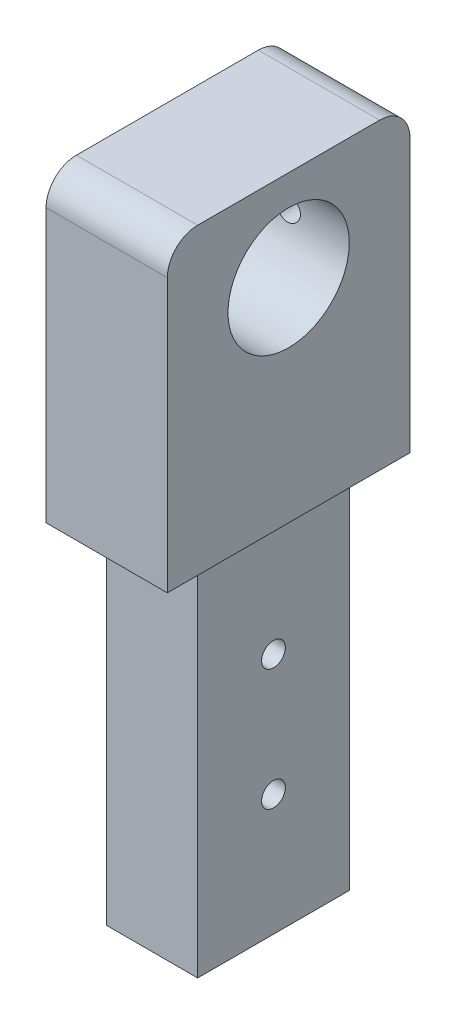
SolidWorks part; units mm, degrees
material "6061-T6 (SS)"
ref_plane "Front Plane" through (0, 0, 0) normal (0, 0, 1) x (1, 0, 0)
ref_plane "Top Plane" through (0, 0, 0) normal (0, 1, 0) x (1, 0, 0)
ref_plane "Right Plane" through (0, 0, 0) normal (1, 0, 0) x (0, 0, -1)
sketch "Sketch2" plane through (0, 0, 0) normal (0, 1, 0) x (1, 0, 0)
  line L1 (-9.525, -15.875) -> (9.525, -15.875)
  line L2 (-9.525, -15.875) -> (-9.525, 15.875)
  line L3 (-9.525, 15.875) -> (9.525, 15.875)
  line L4 (9.525, -15.875) -> (9.525, 15.875)
  line L5 (-9.525, -15.875) -> (9.525, 15.875) construction
  line L6 (-9.525, 15.875) -> (9.525, -15.875) construction
  point P0 (0, 0)
  dimension "D1" = 19.05
  dimension "D2" = 31.75
extrude "Boss-Extrude1" add sketch "Sketch2" along normal blind 76.2
sketch "Sketch3" plane through (0, 76.2, 0) normal (0, 1, 0) x (1, 0, 0)
  line L1 (-12.7, -25.4) -> (12.7, -25.4)
  line L2 (-12.7, -25.4) -> (-12.7, 25.4)
  line L3 (-12.7, 25.4) -> (12.7, 25.4)
  line L4 (12.7, -25.4) -> (12.7, 25.4)
  line L5 (-12.7, -25.4) -> (12.7, 25.4) construction
  line L6 (-12.7, 25.4) -> (12.7, -25.4) construction
  point P0 (0, 0)
  dimension "D1" = 25.4
  dimension "D2" = 50.8
extrude "Boss-Extrude2" add sketch "Sketch3" along normal blind 63.5
fillet "Fillet1" radius 6.35 2 edges at (0, 139.7, -25.4) (0, 139.7, 25.4)
sketch "Sketch4" plane through (12.7, 0, 0) normal (1, 0, 0) x (0, 0, -1)
  line L0 (-25.4, 76.2) -> (25.4, 76.2) construction
  circle A0 centre (0, 120.65) radius 12.7
  dimension "D1" = 25.4
  dimension "D2" = 44.45
extrude "Cut-Extrude1" cut sketch "Sketch4" against normal through all
sketch "Sketch5" plane through (0, 0, -25.4) normal (0, 0, -1) x (-1, 0, 0)
  circle A0 centre (0, 120.65) radius 2.4892
  dimension "D1" = 4.9784
extrude "Cut-Extrude2" cut sketch "Sketch5" against normal up to surface (12.7 mm away) up to face at (-12.7, 120.65, -12.7)
sketch "Sketch6" plane through (-9.525, 0, 0) normal (-1, 0, 0) x (0, 0, 1)
  line L0 (0, 0) -> (0, 76.2) construction
  line L1 (-15.875, 0) -> (15.875, 0) construction
  line L2 (-15.875, 76.2) -> (15.875, 76.2) construction
  circle A0 centre (0, 25.4) radius 2.4892
  circle A1 centre (0, 50.8) radius 2.4892
  dimension "D1" = 4.9784
  dimension "D2" = 25.4
  dimension "D3" = 25.4
extrude "Cut-Extrude3" cut sketch "Sketch6" against normal up to next
